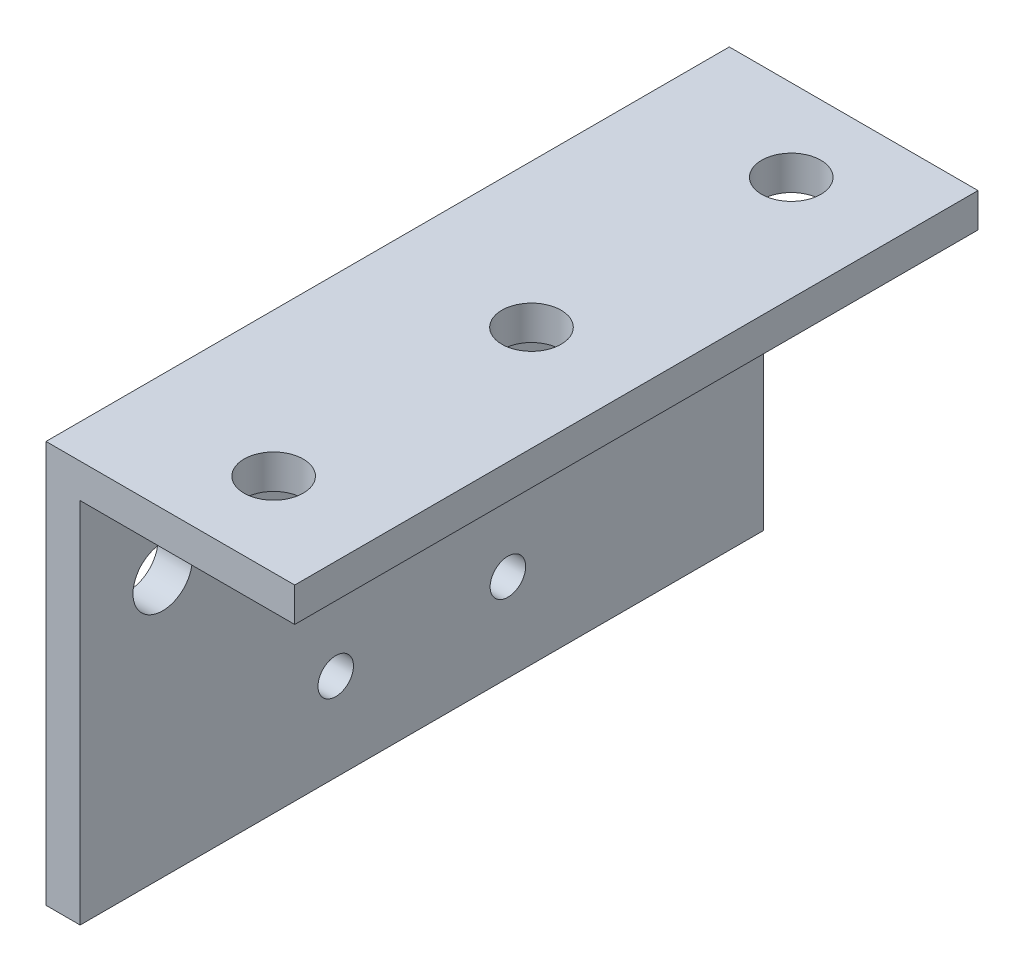
SolidWorks part; units mm, degrees
material "6061 Alloy"
ref_plane "Front Plane" through (0, 0, 0) normal (0, 0, 1) x (1, 0, 0)
ref_plane "Top Plane" through (0, 0, 0) normal (0, 1, 0) x (1, 0, 0)
ref_plane "Right Plane" through (0, 0, 0) normal (1, 0, 0) x (0, 0, -1)
sketch "Sketch1" plane through (0, 0, 0) normal (0, 0, 1) x (1, 0, 0)
  line L0 (0, 0) -> (0, 37.338)
  line L1 (0, 37.338) -> (23.114, 37.338)
  line L2 (23.114, 37.338) -> (23.114, 34.163)
  line L3 (0, 0) -> (3.175, 0)
  line L4 (3.175, 0) -> (3.175, 34.163)
  line L5 (3.175, 34.163) -> (23.114, 34.163)
  dimension "D1" = 37.338
  dimension "D2" = 23.114
  dimension "D3" = 3.175
  dimension "D4" = 3.175
extrude "Boss-Extrude1" add sketch "Sketch1" along normal blind 63.5
sketch "Sketch21" plane through (0, 0, 0) normal (-1, 0, 0) x (0, 0, 1)
  line L0 (31.75, 0) -> (31.75, 37.338) construction
  line L1 (63.5, 0) -> (0, 0) construction
  line L2 (63.5, 37.338) -> (0, 37.338) construction
  point P3 (31.75, 18.669)
sketch "Sketch28" plane through (0, 37.338, 0) normal (0, 1, 0) x (1, 0, 0)
  line L0 (23.114, -31.75) -> (0, -31.75) construction
  line L2 (23.114, -63.5) -> (23.114, 0) construction
  point P3 (11.557, -31.75)
sketch "Sketch29" plane through (0, 0, 0) normal (-1, 0, 0) x (0, 0, 1)
  line L0 (0, 24.2082) -> (63.5, 24.2082) construction
  line L1 (0, 37.338) -> (0, 0) construction
  line L2 (63.5, 37.338) -> (63.5, 0) construction
sketch "Sketch30" plane through (0, 37.338, 0) normal (0, 1, 0) x (1, 0, 0)
  line L0 (13.3686, 0) -> (13.3686, -63.5) construction
  line L1 (23.114, 0) -> (0, 0) construction
  line L2 (23.114, -63.5) -> (0, -63.5) construction
  line L3 (0, -63.5) -> (0, 0) construction
  dimension "D1" = 13.3686
sketch "Sketch31" plane through (0, 0, 0) normal (-1, 0, 0) x (0, 0, 1)
  line L0 (31.75, 24.2082) -> (10.16, 24.2082) construction
  line L1 (0, 24.2082) -> (63.5, 24.2082) construction
  line L2 (31.75, 24.2082) -> (53.34, 24.2082) construction
sketch "Sketch32" plane through (0, 37.338, 0) normal (0, 1, 0) x (1, 0, 0)
  line L0 (13.3686, -31.75) -> (13.3686, -53.34) construction
  line L1 (13.3686, 0) -> (13.3686, -63.5) construction
  line L2 (13.3686, -31.75) -> (13.3686, -10.16) construction
hole_wizard "M5 Clearance Hole1" positions "Sketch35" profile "Sketch36" hole size "M5" standard "ANSI Metric" end condition through all
sketch "Sketch35" plane through (0, 0, 0) normal (-1, 0, 0) x (0, 0, 1)
  line L0 (0, 24.2082) -> (63.5, 24.2082) construction
  point P0 (55.8413, 24.2082)
sketch "Sketch36" plane through (0, 24.2082, 55.8413) normal (0, 1, 0) x (0, 0, 1)
  line L0 (0, 0) -> (0, 23.114)
  line L1 (0, 23.114) -> (2.75, 23.114)
  line L2 (2.75, 23.114) -> (2.75, 0)
  line L5 (2.75, 0) -> (0, 0)
  line L11 (0, -6.35) -> (0, 107.95) construction
  dimension "Thru Hole Dia." = 5.5
  dimension "Thru Hole Depth" = 23.114
hole_wizard "M5 Clearance Hole2" positions "Sketch37" profile "Sketch38" hole size "M5" standard "ANSI Metric" end condition through all
sketch "Sketch37" plane through (0, 0, 0) normal (-1, 0, 0) x (0, 0, 1)
  line L0 (0, 24.2082) -> (63.5, 24.2082) construction
  point P0 (7.6776, 24.2082)
sketch "Sketch38" plane through (0, 24.2082, 7.6776) normal (0, 1, 0) x (0, 0, 1)
  line L0 (0, 0) -> (0, 23.114)
  line L1 (0, 23.114) -> (2.75, 23.114)
  line L2 (2.75, 23.114) -> (2.75, 0)
  line L5 (2.75, 0) -> (0, 0)
  line L11 (0, -6.35) -> (0, 107.95) construction
  dimension "Thru Hole Dia." = 5.5
  dimension "Thru Hole Depth" = 23.114
hole_wizard "M5 Clearance Hole3" positions "Sketch39" profile "Sketch40" hole size "M5" standard "ANSI Metric" end condition through all
sketch "Sketch39" plane through (0, 37.338, 0) normal (0, 1, 0) x (1, 0, 0)
  point P0 (13.3686, -31.75)
sketch "Sketch40" plane through (13.3686, 37.338, 31.75) normal (1, 0, 0) x (0, 0, 1)
  line L0 (0, 0) -> (0, 37.338)
  line L1 (0, 37.338) -> (2.75, 37.338)
  line L2 (2.75, 37.338) -> (2.75, 0)
  line L5 (2.75, 0) -> (0, 0)
  line L11 (0, -6.35) -> (0, 107.95) construction
  dimension "Thru Hole Dia." = 5.5
  dimension "Thru Hole Depth" = 37.338
hole_wizard "M5 Clearance Hole4" positions "Sketch43" profile "Sketch44" hole size "M5" standard "ANSI Metric" end condition through all
sketch "Sketch43" plane through (0, 37.338, 0) normal (0, 1, 0) x (1, 0, 0)
  line L0 (13.3686, 0) -> (13.3686, -63.5) construction
  point P0 (13.3686, -55.7137)
sketch "Sketch44" plane through (13.3686, 37.338, 55.7137) normal (1, 0, 0) x (0, 0, 1)
  line L0 (0, 0) -> (0, 37.338)
  line L1 (0, 37.338) -> (2.75, 37.338)
  line L2 (2.75, 37.338) -> (2.75, 0)
  line L5 (2.75, 0) -> (0, 0)
  line L11 (0, -6.35) -> (0, 107.95) construction
  dimension "Thru Hole Dia." = 5.5
  dimension "Thru Hole Depth" = 37.338
hole_wizard "M5 Clearance Hole5" positions "Sketch49" profile "Sketch50" hole size "M5" standard "ANSI Metric" end condition through all
sketch "Sketch49" plane through (0, 37.338, 0) normal (0, 1, 0) x (1, 0, 0)
  line L0 (13.3686, 0) -> (13.3686, -63.5) construction
  line L1 (23.114, 0) -> (0, 0) construction
  point P0 (13.3686, -7.6106)
  point P6 (0, 0)
  point P9 (0, 0)
  dimension "D1" = 7.6106
sketch "Sketch50" plane through (13.3686, 37.338, 7.6106) normal (1, 0, 0) x (0, 0, 1)
  line L0 (0, 0) -> (0, 37.338)
  line L1 (0, 37.338) -> (2.75, 37.338)
  line L2 (2.75, 37.338) -> (2.75, 0)
  line L5 (2.75, 0) -> (0, 0)
  line L11 (0, -6.35) -> (0, 107.95) construction
  dimension "Thru Hole Dia." = 5.5
  dimension "Thru Hole Depth" = 37.338
sketch "Sketch51" plane through (0, 0, 0) normal (-1, 0, 0) x (0, 0, 1)
  line L0 (63.5, 34.163) -> (0, 34.163) construction
  line L1 (39.75, 24.163) -> (23.75, 24.163) construction
  line L2 (39.75, 24.163) -> (39.75, 8.163) construction
  line L3 (39.75, 8.163) -> (23.75, 8.163) construction
  line L4 (23.75, 24.163) -> (23.75, 8.163) construction
  line L5 (39.75, 24.163) -> (23.75, 8.163) construction
  line L6 (39.75, 8.163) -> (23.75, 24.163) construction
  line L7 (31.75, 37.338) -> (31.75, 0) construction
  line L8 (63.5, 37.338) -> (0, 37.338) construction
  line L9 (63.5, 0) -> (0, 0) construction
  circle A0 centre (31.75, 16.163) radius 5 construction
  point P0 (31.75, 16.163)
  dimension "D4" = 10
  dimension "D1" = 10
  dimension "D2" = 16
  dimension "D3" = 16
hole_wizard "Tap Drill for M4x0.7 Tap2" positions "Sketch52" profile "Sketch53" hole size "M4x0.7" standard "ANSI Metric" end condition through all
sketch "Sketch52" plane through (0, 0, 0) normal (-1, 0, 0) x (0, 0, 1)
  point P0 (23.75, 24.163)
  point P3 (23.75, 8.163)
  point P6 (39.75, 8.163)
  point P9 (39.75, 24.163)
sketch "Sketch53" plane through (0, 24.163, 23.75) normal (0, 1, 0) x (0, 0, 1)
  line L0 (0, 0) -> (0, 23.114)
  line L1 (0, 23.114) -> (1.65, 23.114)
  line L2 (1.65, 23.114) -> (1.65, 0)
  line L5 (1.65, 0) -> (0, 0)
  line L11 (0, -6.35) -> (0, 107.95) construction
  dimension "Thru Hole Dia." = 3.3
  dimension "Thru Hole Depth" = 23.114
sketch "Sketch54" plane through (0, 37.338, 0) normal (0, 1, 0) x (1, 0, 0)
  line L0 (0, -31.75) -> (23.114, -31.75) construction
  line L1 (0, -63.5) -> (0, 0) construction
  line L2 (23.114, -63.5) -> (23.114, 0) construction
